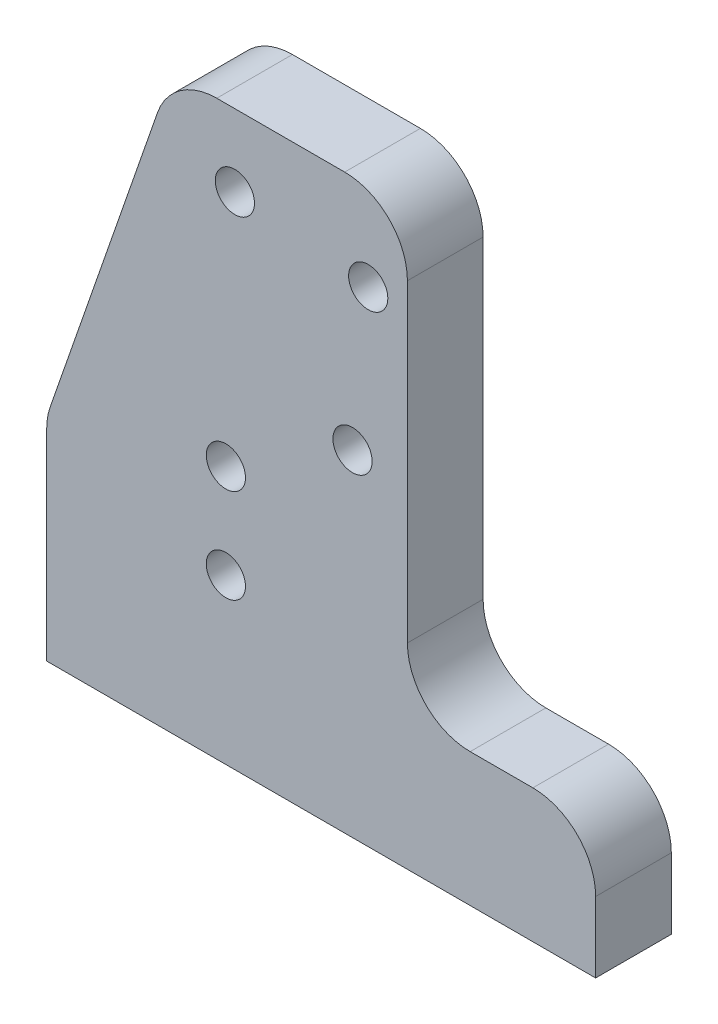
SolidWorks part; units mm, degrees
other "Markup1"
sketch "Sketch26" plane through (35, 0, 4.826) normal (0.2759, -0.8282, 0.4878) x (0.8301, -0.0505, -0.5553)
material "6061 Alloy"
ref_plane "Front" through (0, 0, 0) normal (0, 0, 1) x (1, 0, 0)
ref_plane "Top" through (0, 0, 0) normal (0, 1, 0) x (1, 0, 0)
ref_plane "Right" through (0, 0, 0) normal (1, 0, 0) x (0, 0, -1)
sketch "Sketch1" plane through (0, 0, 0) normal (0, 0, 1) x (1, 0, 0)
  line L0 (0, 0) -> (0, 13.5)
  line L9 (35, 0) -> (0, 0)
  line L15 (8, 36.5) -> (23, 36.5)
  line L16 (23, 36.5) -> (23, 8.5)
  line L17 (23, 8.5) -> (35, 8.5)
  line L18 (35, 8.5) -> (35, 0)
  line L22 (8, 36.5) -> (0, 13.5)
  dimension "D3" = 13.5
  dimension "D1" = 35
  dimension "D2" = 12
  dimension "D4" = 15
  dimension "D5" = 36.5
  dimension "D6" = 8.5
extrude "Boss-Extrude1" add sketch "Sketch1" along normal blind 4.826 contours L9 region at (14.5579, 15.4228, 0)
hole_wizard "M3x0.5 Tapped Hole2" positions "Sketch13" profile "Sketch14" tap size "M3x0.5" standard "ANSI Metric" end condition through all
sketch "Sketch13" plane through (0, 0, 4.826) normal (0, 0, 1) x (1, 0, 0)
  line L3 (8, 36.5) -> (23, 36.5) construction
  point P5 (12, 31.9)
  dimension "D1" = 4.6
  dimension "D2" = 12
sketch "Sketch14" plane through (12, 31.9, 4.826) normal (1, 0, 0) x (0, -1, 0)
  line L0 (0, 0) -> (0, 4.826)
  line L1 (0, 4.826) -> (1.25, 4.826)
  line L2 (1.25, 4.826) -> (1.25, 0)
  line L5 (1.25, 0) -> (0, 0)
  line L11 (0, -6.35) -> (0, 107.95) construction
  dimension "Thru Tap Drill Dia." = 2.5
  dimension "Thru Tap Drill Depth" = 4.826
cosmetic thread "Hole Thread1" parameters "D2"=3
sketch "Sketch16" plane through (0, 0, 0) normal (0, -1, 0) x (1, 0, 0)
  line L0 (0, 4.826) -> (0, 0) construction
  line L3 (0, 2.413) -> (42.6944, 2.413) construction
  point P0 (28.73, 2.413)
  point P1 (16.73, 2.413)
  dimension "D1" = 16.73
  dimension "D2" = 12
hole_wizard "M3x0.5 Tapped Hole3" positions "Sketch17" profile "Sketch18" tap size "M3x0.5" standard "ANSI Metric"
sketch "Sketch17" plane through (0, 0, 0) normal (0, -1, 0) x (-1, 0, 0)
  point P0 (-16.73, -2.413)
  point P3 (-28.73, -2.413)
sketch "Sketch18" plane through (16.73, 0, 2.413) normal (1, 0, 0) x (0, 0, -1)
  line L0 (0, 0) -> (0, 5.7511)
  line L1 (0, 5.7511) -> (1.25, 5)
  line L2 (1.25, 5) -> (1.25, 0)
  line L5 (1.25, 0) -> (0, 0)
  line L10 (0, 5.7511) -> (-1.25, 5) construction
  line L11 (0, -6.35) -> (0, 107.95) construction
  dimension "Tap Drill Dia." = 2.5
  dimension "Tap Drill Depth" = 5
  dimension "Drill Angle" = 118
fillet "Fillet2" radius 4 5 edges at (35, 8.5, 2.413) (23, 8.5, 2.413) (23, 36.5, 2.413) (0, 13.5, 2.413) (8, 36.5, 2.413)
sketch "Sketch19" plane through (0, 0, 4.826) normal (0, 0, 1) x (1, 0, 0)
  circle A0 centre (19.5, 21.4) radius 1.4
  circle A1 centre (12, 31.9) radius 1.25 construction
  point P7 (19.1596, 19.9162)
  dimension "D3" = 2.8
  dimension "D1" = 10.5
  dimension "D2" = 7.5
sketch "Sketch23" plane through (0, 0, 4.826) normal (0, 0, 1) x (1, 0, 0)
  circle A0 centre (20.5, 30.9) radius 1.25
  circle A1 centre (12, 31.9) radius 1.25 construction
  dimension "D3" = 2.5
  dimension "D1" = 8.5
  dimension "D2" = 1
sketch "Sketch28" plane through (0, 0, 4.826) normal (0, 0, 1) x (1, 0, 0)
  circle A0 centre (11.425, 16.46) radius 1.4
  circle A1 centre (11.425, 10.46) radius 1.4
  circle A2 centre (12, 31.9) radius 1.25 construction
  point P6 (12.956, 9.1586)
  point P7 (0, 0)
  point P9 (0, 0)
  point P10 (0, 0)
  dimension "D3" = 2.8
  dimension "D1" = 15.44
  dimension "D2" = 6
  dimension "D5" = 0.575
hole_wizard "M3x0.5 Tapped Hole4" positions "Sketch29" profile "Sketch30" tap size "M3x0.5" standard "ANSI Metric" end condition through all
sketch "Sketch29" plane through (0, 0, 4.826) normal (0, 0, 1) x (1, 0, 0)
  point P0 (19.5, 21.4)
  point P3 (20.5, 30.9)
sketch "Sketch30" plane through (19.5, 21.4, 4.826) normal (1, 0, 0) x (0, -1, 0)
  line L0 (0, 0) -> (0, 4.826)
  line L1 (0, 4.826) -> (1.25, 4.826)
  line L2 (1.25, 4.826) -> (1.25, 0)
  line L5 (1.25, 0) -> (0, 0)
  line L11 (0, -6.35) -> (0, 107.95) construction
  dimension "Thru Tap Drill Dia." = 2.5
  dimension "Thru Tap Drill Depth" = 4.826
cosmetic thread "Hole Thread2" parameters "D2"=3
cosmetic thread "Hole Thread3" parameters "D2"=3
hole_wizard "M3x0.5 Tapped Hole5" positions "Sketch33" profile "Sketch34" tap size "M3x0.5" standard "ANSI Metric" end condition through all
sketch "Sketch33" plane through (0, 0, 4.826) normal (0, 0, 1) x (1, 0, 0)
  point P0 (11.425, 16.46)
  point P3 (11.425, 10.46)
sketch "Sketch34" plane through (11.425, 16.46, 4.826) normal (1, 0, 0) x (0, -1, 0)
  line L0 (0, 0) -> (0, 4.826)
  line L1 (0, 4.826) -> (1.25, 4.826)
  line L2 (1.25, 4.826) -> (1.25, 0)
  line L5 (1.25, 0) -> (0, 0)
  line L11 (0, -6.35) -> (0, 107.95) construction
  dimension "Thru Tap Drill Dia." = 2.5
  dimension "Thru Tap Drill Depth" = 4.826
cosmetic thread "Hole Thread4" parameters "D2"=3
cosmetic thread "Hole Thread5" parameters "D2"=3
